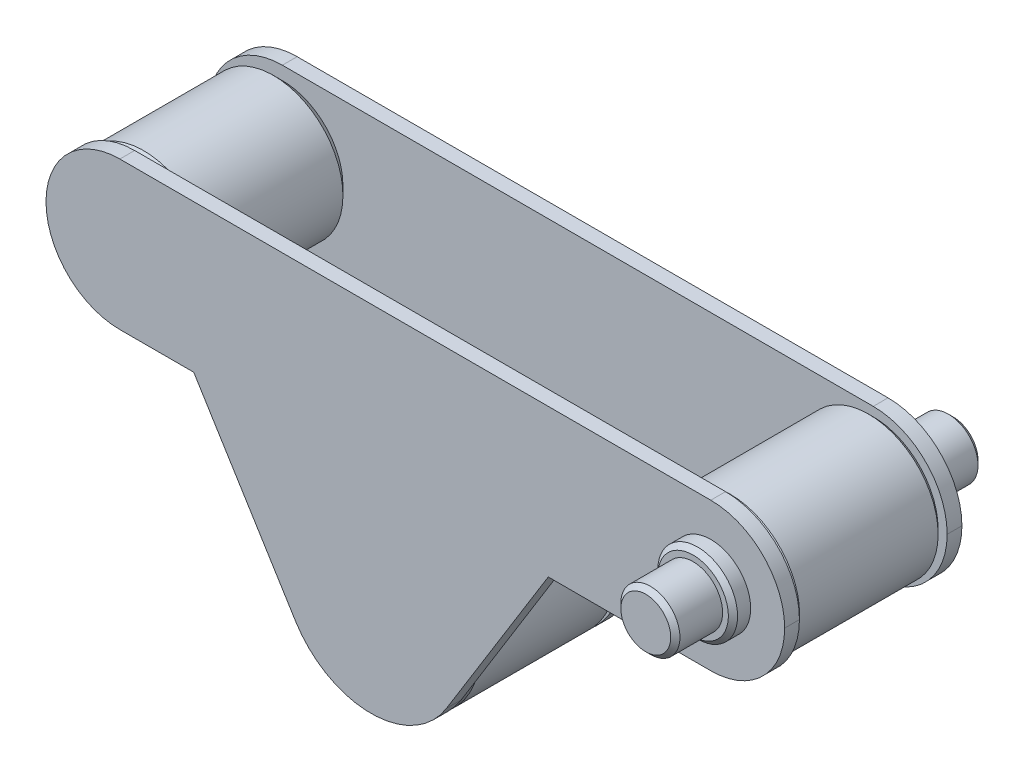
SolidWorks part; units mm, degrees
material "Сталь 3 ГОСТ 535-88"
ref_plane "Спереди" through (0, 0, 0) normal (0, 0, 1) x (1, 0, 0)
ref_plane "Сверху" through (0, 0, 0) normal (0, 1, 0) x (1, 0, 0)
ref_plane "Справа" through (0, 0, 0) normal (1, 0, 0) x (0, 0, -1)
sketch "Эскиз1" plane through (0, 0, 0) normal (1, 0, 0) x (0, 0, -1)
  line L1 (-52, 0) -> (-52, 10)
  line L2 (-52, 10) -> (-36, 10)
  line L3 (-36, 10) -> (-36, 13.5)
  line L4 (-36, 13.5) -> (-25, 13.5)
  line L5 (36, 13.5) -> (36, 10)
  line L6 (36, 10) -> (52, 10)
  line L7 (52, 10) -> (52, 0)
  line L8 (0, 25.8106) -> (0, -23.114) construction
  line L9 (-71.1264, 0) -> (85.8599, 0) construction
  line L10 (-52, 0) -> (52, 0)
  line L11 (25, 13.5) -> (36, 13.5)
  line L13 (25, 13.5) -> (25, 23.5)
  line L14 (25, 23.5) -> (-25, 23.5)
  line L15 (-25, 13.5) -> (-25, 23.5)
  point P12 (52, 5)
  dimension "D1" = 20
  dimension "D2" = 27
  dimension "D3" = 104
  dimension "D4" = 72
  dimension "D5" = 10
  dimension "D6" = 50
revolve "Повернуть1" add sketch "Эскиз1" angle 360 about L9
chamfer "Фаска1" distance 1.56 angle 45 6 edges at (10, 0, 52) (13.5, 0, 36) (10, 0, -52) (23.5, 0, 25) (23.5, 0, -25) (13.5, 0, -36)
sketch "Эскиз2" plane through (0, 0, -25) normal (0, 0, -1) x (-1, 0, 0)
  line L0 (-25, -25) -> (-25, 25)
  line L1 (-25, 25) -> (225, 25)
  line L2 (-25, -25) -> (55, -25)
  line L3 (55, -25) -> (89.4828, -80.7757)
  line L5 (140.5172, -80.7757) -> (175, -25)
  line L6 (175, -25) -> (225, -25)
  line L7 (225, -25) -> (225, 25)
  line L8 (-40.7297, 0) -> (66.8826, 0) construction
  line L9 (115, -95) -> (115, 11.3994) construction
  circle A0 centre (0, 0) radius 13.5 construction
  circle A1 centre (0, 0) radius 13.5
  arc A2 (89.4828, -80.7757) -> (140.5172, -80.7757) centre (115, -65) ccw
  point P6 (142.1605, -95)
  point P9 (0, 0)
  point P19 (0, 0)
  dimension "D6" = 120
  dimension "D4" = 30
  dimension "D1" = 50
  dimension "D2" = 25
  dimension "D3" = 250
  dimension "D5" = 50
  dimension "D7" = 80
extrude "Бобышка-Вытянуть1" add sketch "Эскиз2" along normal blind 5 separate body
fillet "Скругление1" radius 25 4 edges at (25, -25, -27.5) (25, 25, -27.5) (-225, -25, -27.5) (-225, 25, -27.5)
mirror "Зеркальное отражение1" about plane through (0, 0, 0) normal (0, 0, 1) of bodies 104
sketch "Эскиз3" plane through (0, 0, -25) normal (0, 0, 1) x (1, 0, 0)
  arc A1 (-140.5172, -80.7757) -> (-89.4828, -80.7757) centre (-115, -65) ccw construction
  circle A2 centre (-115, -65) radius 30
  point P7 (-85.4147, -60.0291)
  point P9 (0, 0)
extrude "Бобышка-Вытянуть2" add sketch "Эскиз3" along normal up to surface (50 mm away) separate body up to face at (-106, -22.5776, 25)
sketch "Эскиз4" plane through (0, 0, -25) normal (0, 0, 1) x (1, 0, 0)
  circle A0 centre (-200, 0) radius 23.5
  arc A1 (-200, 25) -> (-225, 0) centre (-200, 0) ccw construction
  dimension "D1" = 47
extrude "Бобышка-Вытянуть3" add sketch "Эскиз4" along normal up to surface (50 mm away) separate body up to face at (-106, -22.5776, 25)
chamfer "Фаска2" distance 3 angle 45 2 edges at (-176.5, 0, 25) (-176.5, 0, -25)
chamfer "Фаска3" distance 2 angle 45 2 edges at (-85, -65, 25) (-85, -65, -25)
